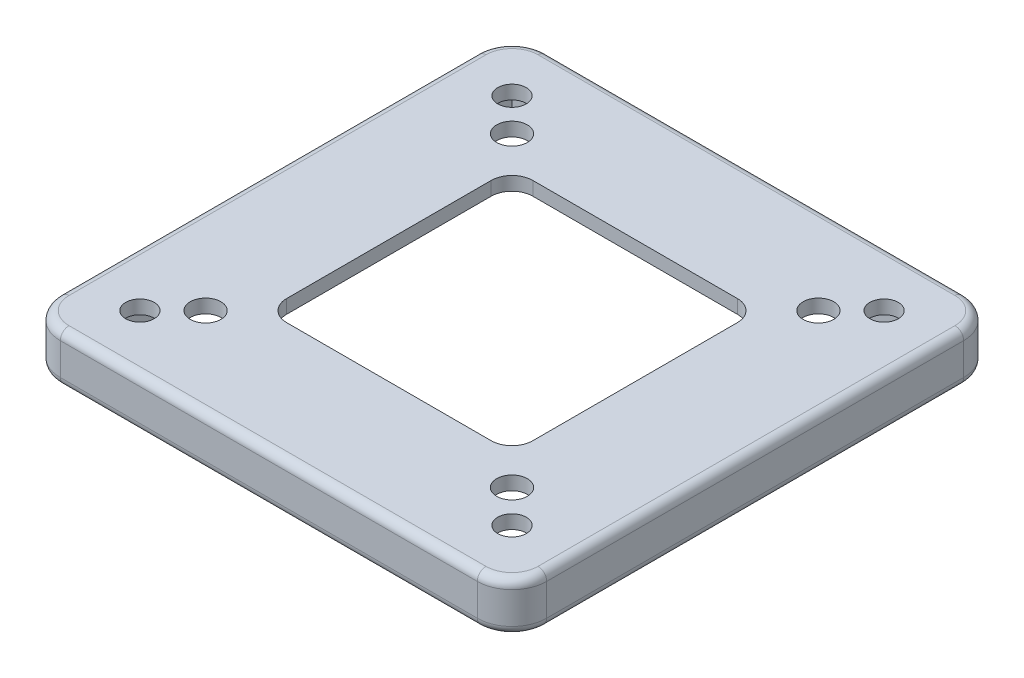
SolidWorks part; units mm, degrees
ref_plane "Front Plane" through (0, 0, 0) normal (0, 0, 1) x (1, 0, 0)
ref_plane "Top Plane" through (0, 0, 0) normal (0, 1, 0) x (1, 0, 0)
ref_plane "Right Plane" through (0, 0, 0) normal (1, 0, 0) x (0, 0, -1)
sketch "Sketch1" plane through (0, 0, 0) normal (0, 1, 0) x (1, 0, 0)
  line L0 (0, 0) -> (-9.2818, 0) construction
  line L1 (-17, 17) -> (17, 17) construction
  line L2 (-17, 17) -> (-17, -17) construction
  line L3 (-17, -17) -> (17, -17) construction
  line L4 (17, 17) -> (17, -17) construction
  line L5 (-17, 17) -> (17, -17) construction
  line L6 (-17, -17) -> (17, 17) construction
  line L7 (-14, 14) -> (14, 14) construction
  line L8 (-14, 14) -> (-14, -14) construction
  line L9 (-14, -14) -> (14, -14) construction
  line L10 (14, 14) -> (14, -14) construction
  line L11 (-14, 14) -> (14, -14) construction
  line L12 (-14, -14) -> (14, 14) construction
  line L17 (-11.25, 11.25) -> (11.25, 11.25)
  line L18 (-11.25, 11.25) -> (-11.25, -11.25)
  line L19 (-25.4, 38.1) -> (25.4, 38.1)
  line L20 (-25.4, 38.1) -> (-25.4, -38.1)
  line L21 (-25.4, -38.1) -> (25.4, -38.1)
  line L22 (25.4, 38.1) -> (25.4, -38.1)
  line L23 (-25.4, 38.1) -> (25.4, -38.1) construction
  line L24 (-25.4, -38.1) -> (25.4, 38.1) construction
  line L25 (-11.25, -11.25) -> (11.25, -11.25)
  line L26 (11.25, 11.25) -> (11.25, -11.25)
  line L27 (-11.25, 11.25) -> (11.25, -11.25) construction
  line L28 (-11.25, -11.25) -> (11.25, 11.25) construction
  line L29 (-12.7, 31.75) -> (0, 31.75) construction
  line L30 (0, 19) -> (0, -19) construction
  line L31 (-25.4, -19) -> (25.4, -19) construction
  line L32 (-25.4, -19) -> (-25.4, 19)
  line L33 (-25.4, 19) -> (25.4, 19) construction
  line L34 (25.4, -19) -> (25.4, 19)
  line L35 (-19, 19) -> (-19, -19) construction
  line L36 (19, -19) -> (19, 19) construction
  line L37 (-19, 0) -> (19, 0) construction
  line L38 (-19, 19) -> (19, 19) construction
  line L39 (-19, -19) -> (19, -19) construction
  line L40 (-25.35, 25.35) -> (25.35, 25.35)
  line L41 (25.35, -25.35) -> (25.35, 25.35)
  line L42 (-25.35, -25.35) -> (25.35, -25.35)
  line L43 (-25.35, 25.35) -> (-25.35, -25.35)
  circle A0 centre (-17, 17) radius 1.3
  circle A1 centre (-17, -17) radius 1.3
  circle A2 centre (17, -17) radius 1.3
  circle A3 centre (17, 17) radius 1.3
  circle A4 centre (-14, 14) radius 1.4
  circle A5 centre (14, 14) radius 1.4
  circle A6 centre (14, -14) radius 1.4
  circle A7 centre (-14, -14) radius 1.4
  circle A8 centre (-12.7, 31.75) radius 2.4892
  circle A9 centre (0, 31.75) radius 2.4892
  circle A10 centre (12.7, 31.75) radius 2.4892
  circle A11 centre (12.7, -31.75) radius 2.4892
  circle A12 centre (0, -31.75) radius 2.4892
  circle A13 centre (-12.7, -31.75) radius 2.4892
  point P0 (0, 0)
  point P10 (0, 0)
  point P19 (0, 0)
  point P25 (0, 0)
  point P53 (0, 0)
  point P58 (0, 0)
  dimension "D3" = 2.6
  dimension "D6" = 2.8
  dimension "D11" = 4.9784
  dimension "D12" = 6.35
  dimension "D13" = 12.7
  dimension "D1" = 34
  dimension "D2" = 34
  dimension "D4" = 28
  dimension "D5" = 28
  dimension "D7" = 50.8
  dimension "D8" = 76.2
  dimension "D9" = 22.5
  dimension "D10" = 22.5
  dimension "D15" = 12.7
  dimension "D16" = 38
  dimension "D17" = 38
  dimension "D18" = 6.35
  dimension "D14" = 3
extrude "Boss-Extrude1" add sketch "Sketch1" along normal blind 6.35 contours L26 L21 L22 L19 L20 L18 L25 A7 A6 A5 A4 A3 A2 A1 A0 region at (0, 0, -24.633)
shell "Shell1" thickness 1.5875 removed face at (-14, 0, 15.4)
sketch "Sketch6" plane through (0, 4.7625, 0) normal (0, -1, 0) x (1, 0, 0)
  line L4 (-23.7625, -23.7625) -> (23.7625, -23.7625)
  line L5 (23.7625, -23.7625) -> (23.7625, 23.7625)
  line L6 (23.7625, 23.7625) -> (-23.7625, 23.7625)
  line L7 (-23.7625, 23.7625) -> (-23.7625, -23.7625)
  line L8 (-23.7625, -23.7625) -> (23.7625, -23.7625)
  line L9 (23.7625, -23.7625) -> (23.7625, 23.7625)
  line L10 (23.7625, 23.7625) -> (-23.7625, 23.7625)
  line L11 (-23.7625, 23.7625) -> (-23.7625, -23.7625)
  line L12 (-12.8375, 11.248) -> (-12.8375, -11.248)
  line L13 (11.248, 12.8375) -> (-11.248, 12.8375)
  line L14 (12.8375, -11.248) -> (12.8375, 11.248)
  line L15 (-11.248, -12.8375) -> (11.248, -12.8375)
  line L16 (-12.8375, 11.248) -> (-12.8375, -11.248)
  line L17 (11.248, 12.8375) -> (-11.248, 12.8375)
  line L18 (12.8375, -11.248) -> (12.8375, 11.248)
  line L19 (-11.248, -12.8375) -> (11.248, -12.8375)
  arc A12 (-14.1125, -16.9854) -> (-11.248, -12.8375) centre (-14, -14) ccw
  arc A13 (-16.9854, -14.1125) -> (-14.1125, -16.9854) centre (-17, -17) ccw
  arc A14 (-12.8375, -11.248) -> (-16.9854, -14.1125) centre (-14, -14) ccw
  arc A15 (-16.9854, 14.1125) -> (-12.8375, 11.248) centre (-14, 14) ccw
  arc A16 (-14.1125, 16.9854) -> (-16.9854, 14.1125) centre (-17, 17) ccw
  arc A17 (-11.248, 12.8375) -> (-14.1125, 16.9854) centre (-14, 14) ccw
  arc A18 (14.1125, 16.9854) -> (11.248, 12.8375) centre (14, 14) ccw
  arc A19 (16.9854, 14.1125) -> (14.1125, 16.9854) centre (17, 17) ccw
  arc A20 (12.8375, 11.248) -> (16.9854, 14.1125) centre (14, 14) ccw
  arc A21 (16.9854, -14.1125) -> (12.8375, -11.248) centre (14, -14) ccw
  arc A22 (14.1125, -16.9854) -> (16.9854, -14.1125) centre (17, -17) ccw
  arc A23 (11.248, -12.8375) -> (14.1125, -16.9854) centre (14, -14) ccw
  arc A24 (-14.1125, -16.9854) -> (-11.248, -12.8375) centre (-14, -14) ccw
  arc A25 (-16.9854, -14.1125) -> (-14.1125, -16.9854) centre (-17, -17) ccw
  arc A26 (-12.8375, -11.248) -> (-16.9854, -14.1125) centre (-14, -14) ccw
  arc A27 (-16.9854, 14.1125) -> (-12.8375, 11.248) centre (-14, 14) ccw
  arc A28 (-14.1125, 16.9854) -> (-16.9854, 14.1125) centre (-17, 17) ccw
  arc A29 (-11.248, 12.8375) -> (-14.1125, 16.9854) centre (-14, 14) ccw
  arc A30 (14.1125, 16.9854) -> (11.248, 12.8375) centre (14, 14) ccw
  arc A31 (16.9854, 14.1125) -> (14.1125, 16.9854) centre (17, 17) ccw
  arc A32 (12.8375, 11.248) -> (16.9854, 14.1125) centre (14, 14) ccw
  arc A33 (16.9854, -14.1125) -> (12.8375, -11.248) centre (14, -14) ccw
  arc A34 (14.1125, -16.9854) -> (16.9854, -14.1125) centre (17, -17) ccw
  arc A35 (11.248, -12.8375) -> (14.1125, -16.9854) centre (14, -14) ccw
  dimension "D1" = 0
  dimension "D2" = 0
extrude "Boss-Extrude4" add sketch "Sketch6" along normal blind 1.7625
sketch "Sketch4" plane through (0, 0, 0) normal (0, -1, 0) x (1, 0, 0)
  line L1 (-19, 19) -> (19, 19)
  line L2 (-19, 19) -> (-19, -19)
  line L3 (-19, -19) -> (19, -19)
  line L4 (19, 19) -> (19, -19)
  line L5 (-19, 19) -> (19, -19) construction
  line L6 (-19, -19) -> (19, 19) construction
  line L20 (-23.7625, -23.7625) -> (23.7625, -23.7625)
  line L21 (-23.7625, 23.7625) -> (-23.7625, -23.7625)
  line L22 (23.7625, 23.7625) -> (-23.7625, 23.7625)
  line L23 (23.7625, -23.7625) -> (23.7625, 23.7625)
  line L24 (-23.7625, -23.7625) -> (23.7625, -23.7625)
  line L25 (-23.7625, 23.7625) -> (-23.7625, -23.7625)
  line L26 (23.7625, 23.7625) -> (-23.7625, 23.7625)
  line L27 (23.7625, -23.7625) -> (23.7625, 23.7625)
  point P0 (0, 0)
  line M7 (23.7625, -23.7625) -> (-23.7625, -23.7625)
  line M8 (-23.7625, -23.7625) -> (-23.7625, 23.7625)
  line M9 (-23.7625, 23.7625) -> (23.7625, 23.7625)
  line M10 (23.7625, 23.7625) -> (23.7625, -23.7625)
  dimension "D1" = 0
  dimension "D2" = 4.7625
  dimension "D3" = 4.7625
extrude "Boss-Extrude3" add sketch "Sketch4" against normal up to surface (3 mm away) contours L1 L4 L3 L2 M7 M10 M9 M8 region at (-23.0904, 0, 0) up to face at (0, 3, 0)
sketch "Sketch5" plane through (0, 0, 0) normal (0, -1, 0) x (1, 0, 0)
  line L1 (-19, 19) -> (19, 19)
  line L2 (-19, 19) -> (-19, -19)
  line L3 (-19, -19) -> (19, -19)
  line L4 (19, 19) -> (19, -19)
  line L5 (-19, 19) -> (19, -19) construction
  line L6 (-19, -19) -> (19, 19) construction
  point P0 (0, 0)
  arc M5 (16.9854, 14.1125) -> (19, 14.9173) centre (17, 17) ccw
  arc M7 (19, -14.9173) -> (16.9854, -14.1125) centre (17, -17) ccw
  arc M8 (16.9854, -14.1125) -> (12.8375, -11.248) centre (14, -14) ccw
  line M9 (12.8375, -11.248) -> (12.8375, 11.248)
  arc M10 (12.8375, 11.248) -> (16.9854, 14.1125) centre (14, 14) ccw
  arc M11 (14.1125, -16.9854) -> (14.9173, -19) centre (17, -17) ccw
  arc M13 (-14.9173, -19) -> (-14.1125, -16.9854) centre (-17, -17) ccw
  arc M14 (-14.1125, -16.9854) -> (-11.248, -12.8375) centre (-14, -14) ccw
  line M15 (-11.248, -12.8375) -> (11.248, -12.8375)
  arc M16 (11.248, -12.8375) -> (14.1125, -16.9854) centre (14, -14) ccw
  arc M17 (-16.9854, -14.1125) -> (-19, -14.9173) centre (-17, -17) ccw
  arc M19 (-19, 14.9173) -> (-16.9854, 14.1125) centre (-17, 17) ccw
  arc M20 (-16.9854, 14.1125) -> (-12.8375, 11.248) centre (-14, 14) ccw
  line M21 (-12.8375, 11.248) -> (-12.8375, -11.248)
  arc M22 (-12.8375, -11.248) -> (-16.9854, -14.1125) centre (-14, -14) ccw
  arc M23 (-14.1125, 16.9854) -> (-14.9173, 19) centre (-17, 17) ccw
  arc M25 (14.9173, 19) -> (14.1125, 16.9854) centre (17, 17) ccw
  arc M26 (14.1125, 16.9854) -> (11.248, 12.8375) centre (14, 14) ccw
  line M27 (11.248, 12.8375) -> (-11.248, 12.8375)
  arc M28 (-11.248, 12.8375) -> (-14.1125, 16.9854) centre (-14, 14) ccw
  line M33 (11.25, -11.25) -> (-11.25, -11.25)
  line M34 (-11.25, -11.25) -> (-11.25, 11.25)
  line M35 (-11.25, 11.25) -> (11.25, 11.25)
  line M36 (11.25, 11.25) -> (11.25, -11.25)
  circle M37 centre (-17, -17) radius 1.3
  circle M38 centre (-17, 17) radius 1.3
  circle M39 centre (17, 17) radius 1.3
  circle M40 centre (17, -17) radius 1.3
  circle M41 centre (-14, -14) radius 1.4
  circle M42 centre (14, -14) radius 1.4
  circle M43 centre (14, 14) radius 1.4
  circle M44 centre (-14, 14) radius 1.4
  dimension "D1" = 38
  dimension "D2" = 38
extrude "Cut-Extrude2" cut sketch "Sketch5" against normal up to surface (3 mm away) contours L4 L1 L2 L3 M25 M26 M27 M28 M23 M19 M20 M21 M22 M17 M13 M14 M15 M16 M11 M7 M8 M9 M10 M5 M36 M33 M34 M35 M37 M39 M41 M43 M44 M42 M40 M38 | M23 M28 M27 M26 M25 | M11 M16 M15 M14 M13 | M5 M10 M9 M8 M7 | M17 M22 M21 M20 M19 region at (-16.9586, 0, 18.4626) region at (0, 0, 16.1115) region at (-16.1115, 0, 0) region at (16.1115, 0, 0) region at (0, 0, -16.1115) up to face at (-16.5625, 3, 0)
sketch "Sketch8" plane through (0, 6.35, 0) normal (0, 1, 0) x (1, 0, 0)
  line L1 (-29.1816, 27.6885) -> (29.1816, 27.6885)
  line L2 (-29.1816, 27.6885) -> (-29.1816, -27.6885)
  line L3 (-29.1816, -27.6885) -> (29.1816, -27.6885)
  line L4 (29.1816, 27.6885) -> (29.1816, -27.6885)
  line L5 (-29.1816, 27.6885) -> (29.1816, -27.6885) construction
  line L6 (-29.1816, -27.6885) -> (29.1816, 27.6885) construction
  point P0 (0, 0)
extrude "Cut-Extrude3" cut sketch "Sketch8" against normal blind 1.85
sketch "Sketch9" plane through (0, 3, 0) normal (0, -1, 0) x (1, 0, 0)
  line L1 (-19, 19) -> (19, 19)
  line L2 (-19, 19) -> (-19, -19)
  line L3 (-19, -19) -> (19, -19)
  line L4 (19, 19) -> (19, -19)
  line L5 (-19, 19) -> (19, -19) construction
  line L6 (-19, -19) -> (19, 19) construction
  point P0 (0, 0)
extrude "Cut-Extrude4" cut sketch "Sketch9" against normal blind 0.25
sketch "Sketch10" plane through (0, 0, 0) normal (0, -1, 0) x (1, 0, 0)
  line L0 (-25.35, -25.35) -> (-25.35, 25.35) construction
  line L1 (-22.225, 22.225) -> (22.225, 22.225)
  line L2 (-22.225, 22.225) -> (-22.225, -22.225)
  line L3 (-22.225, -22.225) -> (22.225, -22.225)
  line L4 (22.225, 22.225) -> (22.225, -22.225)
  line L5 (-22.225, 22.225) -> (22.225, -22.225) construction
  line L6 (-22.225, -22.225) -> (22.225, 22.225) construction
  line L7 (-25.35, -25.35) -> (-25.35, 25.35)
  line L12 (-25.35, -25.35) -> (25.35, -25.35)
  line L13 (25.35, -25.35) -> (25.35, 25.35)
  line L14 (25.35, 25.35) -> (-25.35, 25.35)
  line L15 (-25.35, 25.35) -> (-25.35, -25.35)
  line L16 (-25.35, -25.35) -> (25.35, -25.35)
  line L17 (25.35, -25.35) -> (25.35, 25.35)
  line L18 (25.35, 25.35) -> (-25.35, 25.35)
  line L19 (-25.35, 25.35) -> (-25.35, -25.35)
  point P0 (0, 0)
  line M9 (-25.35, -25.35) -> (25.35, -25.35)
  line M10 (25.35, -25.35) -> (25.35, 25.35)
  line M11 (25.35, 25.35) -> (-25.35, 25.35)
  line M12 (-25.35, 25.35) -> (-25.35, -25.35)
  dimension "D1" = 44.45
  dimension "D2" = 44.45
  dimension "D3" = 0
extrude "Cut-Extrude5" cut sketch "Sketch10" against normal through all contours L1 L4 L3 L2 M12 M9 M10 M11 region at (-24.633, 0, 0)
fillet "Fillet2" radius 1.905 4 edges at (-11.25, 3.875, -11.25) (-11.25, 3.875, 11.25) (11.25, 3.875, -11.25) (11.25, 3.875, 11.25)
fillet "Fillet1" radius 3.175 4 edges at (-22.225, 2.25, 22.225) (22.225, 2.25, -22.225) (22.225, 2.25, 22.225) (-22.225, 2.25, -22.225)
fillet "Fillet3" radius 0.7937 16 edges at (-21.2951, 0, -21.2951) (-22.225, 0, 0) (-21.2951, 0, 21.2951) (0, 0, 22.225) (21.2951, 0, 21.2951) (22.225, 0, 0) (21.2951, 0, -21.2951) (-21.2951, 4.5, 21.2951) (0, 4.5, 22.225) (21.2951, 4.5, 21.2951) (22.225, 4.5, 0) (21.2951, 4.5, -21.2951) (0, 4.5, -22.225) (-21.2951, 4.5, -21.2951) (0, 0, -22.225) (-22.225, 4.5, 0)
